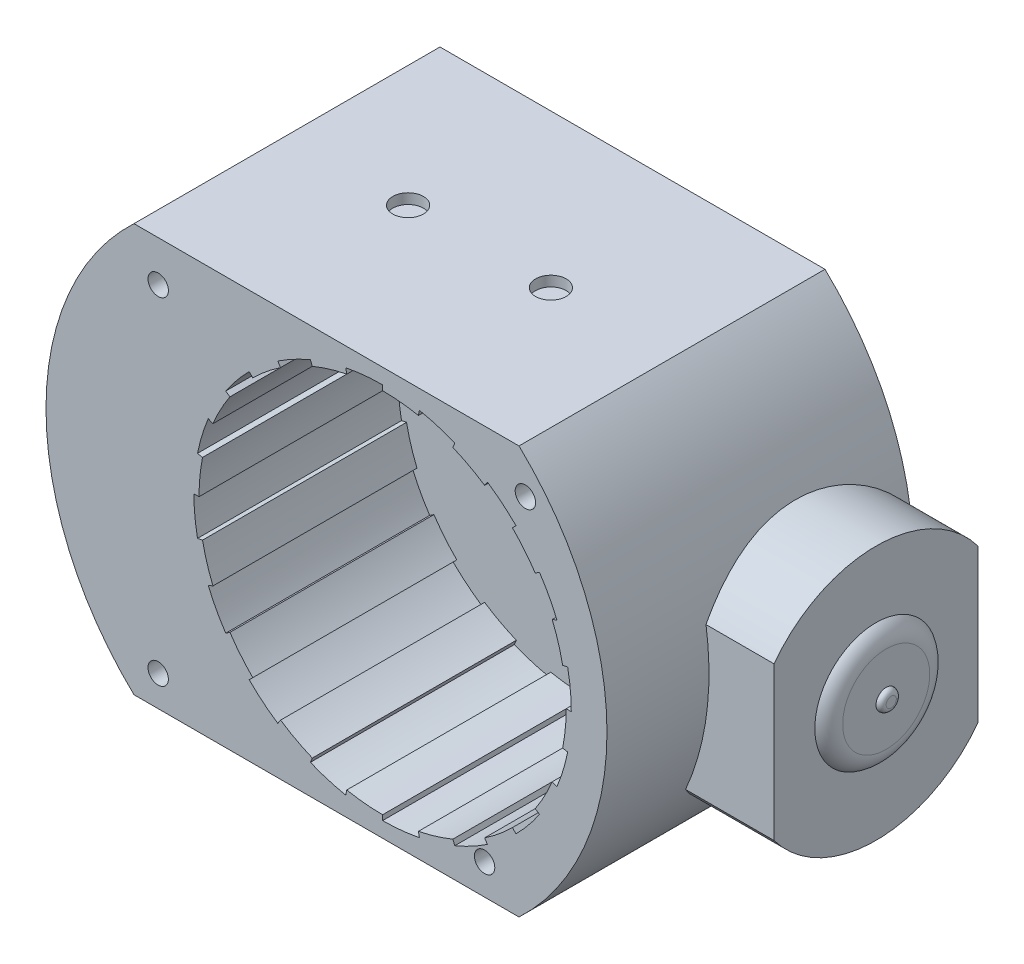
SolidWorks part; units mm, degrees
ref_plane "Alzado" through (0, 0, 0) normal (0, 0, 1) x (1, 0, 0)
ref_plane "Planta" through (0, 0, 0) normal (0, 1, 0) x (1, 0, 0)
ref_plane "Vista lateral" through (0, 0, 0) normal (1, 0, 0) x (0, 0, -1)
sketch "Croquis1" plane through (0, 0, 0) normal (0, 0, 1) x (1, 0, 0)
  line L0 (-27.5, -20) -> (27.5, -20)
  line L1 (-27.5, -20) -> (-27.5, 20)
  line L2 (27.5, -20) -> (27.5, 20)
  line L3 (-27.5, 20) -> (27.5, 20)
  line L4 (-27.5, -20) -> (27.5, 20) construction
  line L5 (27.5, -20) -> (-27.5, 20) construction
  circle A0 centre (0, 0) radius 27.5
  point P1 (0, 0)
  dimension "D1" = 55
  dimension "D2" = 40
extrude "Saliente-Extruir1" add sketch "Croquis1" along normal mid plane 30 contours L3 A0 L0 region at (0, 0, 0)
sketch "Croquis2" plane through (0, 0, 15) normal (0, 0, 1) x (1, 0, 0)
  line L0 (27.5, 0) -> (5.5, 0) construction
  line L1 (5.5, 0) -> (5.5, 18.5)
  line L2 (5.5, 0) -> (9.1092, 18.1445)
  line L3 (5.5, 0) -> (12.5796, 17.0918)
  line L4 (5.5, 0) -> (15.778, 15.3822)
  line L5 (5.5, 0) -> (18.5815, 13.0815)
  line L6 (5.5, 0) -> (20.8822, 10.278)
  line L7 (5.5, 0) -> (22.5918, 7.0796)
  line L8 (5.5, 0) -> (23.6445, 3.6092)
  line L9 (5.5, 0) -> (24, 0)
  line L10 (5.5, 0) -> (23.6445, -3.6092)
  line L11 (5.5, 0) -> (22.5918, -7.0796)
  line L12 (5.5, 0) -> (20.8822, -10.278)
  line L13 (5.5, 0) -> (18.5815, -13.0815)
  line L14 (5.5, 0) -> (15.778, -15.3822)
  line L15 (5.5, 0) -> (12.5796, -17.0918)
  line L16 (5.5, 0) -> (9.1092, -18.1445)
  line L17 (5.5, 0) -> (5.5, -18.5)
  line L18 (5.5, 0) -> (1.8908, -18.1445)
  line L19 (5.5, 0) -> (-1.5796, -17.0918)
  line L20 (5.5, 0) -> (-4.778, -15.3822)
  line L21 (5.5, 0) -> (-7.5815, -13.0815)
  line L22 (5.5, 0) -> (-9.8822, -10.278)
  line L23 (5.5, 0) -> (-11.5918, -7.0796)
  line L24 (5.5, 0) -> (-12.6445, -3.6092)
  line L25 (5.5, 0) -> (-13, 0)
  line L26 (5.5, 0) -> (-12.6445, 3.6092)
  line L27 (5.5, 0) -> (-11.5918, 7.0796)
  line L28 (5.5, 0) -> (-9.8822, 10.278)
  line L29 (5.5, 0) -> (-7.5815, 13.0815)
  line L30 (5.5, 0) -> (-4.778, 15.3822)
  line L31 (5.5, 0) -> (-1.5796, 17.0918)
  line L32 (5.5, 0) -> (1.8908, 18.1445)
  arc A1 (18.8746, -20) -> (18.8746, 20) centre (0, 0) ccw construction
  circle A2 centre (5.5, 0) radius 18.5
  circle A3 centre (5.5, 0) radius 18
  point P45 (5.5, 0)
  dimension "D1" = 22
  dimension "D2" = 37
  dimension "D3" = 0.5
  dimension "D4" = 32
extrude "Cortar-Extruir1" cut sketch "Croquis2" against normal blind 20 contours L2 A3 L1 | L30 A3 L29 | L31 A3 L30 | L32 A3 L31 | L1 A3 L32 | L3 A3 L2 | L4 A3 L3 | L5 A3 L4 | L6 A3 L5 | L7 A3 L6 | L8 A3 L7 | L9 A3 L8 | L10 A3 L9 | L29 A3 L28 | L28 A3 L27 | L27 A3 L26 | L26 A3 L25 | L25 A3 L24 | L24 A3 L23 | L23 A3 L22 | L22 A3 L21 | L21 A3 L20 | L20 A3 L19 | L19 A3 L18 | L18 A3 L17 | L17 A3 L16 | L16 A3 L15 | L15 A3 L14 | L14 A3 L13 | L13 A3 L12 | L12 A3 L11 | L11 A3 L10 | A3 L1 A2 L32 | A3 L31 A2 L30 | A3 L29 A2 L28 | A3 L27 A2 L26 | A3 L25 A2 L24 | A3 L23 A2 L22 | A3 L21 A2 L20 | A3 L19 A2 L18 | A3 L17 A2 L16 | A3 L15 A2 L14 | A3 L13 A2 L12 | A3 L11 A2 L10 | A3 L9 A2 L8 | A3 L7 A2 L6 | A3 L5 A2 L4 | A3 L3 A2 L2 region at (4.3257, 11.923, 15) region at (6.6743, 11.923, 15) region at (8.9778, 11.4648, 15) region at (11.1477, 10.5661, 15) region at (13.1005, 9.2612, 15) region at (14.7612, 7.6005, 15) region at (16.0661, 5.6477, 15) region at (16.9648, 3.4778, 15) region at (17.423, 1.1743, 15) region at (17.423, -1.1743, 15) region at (16.9648, -3.4778, 15) region at (16.0661, -5.6477, 15) region at (14.7612, -7.6005, 15) region at (13.1005, -9.2612, 15) region at (11.1477, -10.5661, 15) region at (8.9778, -11.4648, 15) region at (6.6743, -11.923, 15) region at (4.3257, -11.923, 15) region at (2.0222, -11.4648, 15) region at (-0.1477, -10.5661, 15) region at (-2.1005, -9.2612, 15) region at (-3.7612, -7.6005, 15) region at (-5.0661, -5.6477, 15) region at (-5.9648, -3.4778, 15) region at (-6.423, -1.1743, 15) region at (-6.423, 1.1743, 15) region at (-5.9648, 3.4778, 15) region at (-5.0661, 5.6477, 15) region at (-3.7612, 7.6005, 15) region at (-2.1005, 9.2612, 15) region at (-0.1477, 10.5661, 15) region at (2.0222, 11.4648, 15) region at (3.7139, 18.1341, 15) region at (10.7895, 17.4372, 15) region at (17.0598, 14.0857, 15) region at (21.5702, 8.5897, 15) region at (23.6341, 1.7861, 15) region at (22.9372, -5.2895, 15) region at (19.5857, -11.5598, 15) region at (14.0897, -16.0702, 15) region at (7.2861, -18.1341, 15) region at (0.2105, -17.4372, 15) region at (-6.0598, -14.0857, 15) region at (-10.5702, -8.5897, 15) region at (-12.6341, -1.7861, 15) region at (-11.9372, 5.2895, 15) region at (-8.5857, 11.5598, 15) region at (-3.0897, 16.0702, 15)
ref_plane "Plano1" through (18.8746, 0, 0) normal (1, 0, 0) x (0, 0, -1)
sketch "Croquis3" plane through (18.8746, 0, 0) normal (1, 0, 0) x (0, 0, -1)
  line L0 (15, -20) -> (15, 20) construction
  line L1 (-15, -20) -> (15, -20) construction
  line L2 (-15, 20) -> (15, 20) construction
  line L3 (-15, 20) -> (-15, -20) construction
  line L4 (15, -20) -> (15, 20)
  line L5 (-15, -20) -> (15, -20)
  line L6 (-15, 20) -> (15, 20)
  line L7 (-15, 20) -> (-15, -20)
  line L8 (-15, -16) -> (15, -16)
  line L9 (5, -3.5) -> (15, -3.5) construction
  line L10 (-5, -20) -> (-5, 20)
  circle A0 centre (5, -3.5) radius 12.5
  dimension "D2" = 25
  dimension "D3" = 10
  dimension "D1" = 4
  dimension "D4" = 20
extrude "Saliente-Extruir2" add sketch "Croquis3" along normal blind 15 contours L4 A0 L10 region at (18.8746, -3.5, -5)
sketch "Croquis4" plane through (0, 0, -5) normal (0, 0, 1) x (1, 0, 0)
  circle A0 centre (5.5, 0) radius 1
  dimension "D1" = 2
extrude "Cortar-Extruir2" cut sketch "Croquis4" against normal through all
sketch "Croquis5" plane through (0, 0, -15) normal (0, 0, -1) x (-1, 0, 0)
  circle A0 centre (-5.5, 0) radius 2.5
  circle A1 centre (-5.5, 0) radius 1 construction
  circle A2 centre (-5.5, 0) radius 1
extrude "Saliente-Extruir3" add sketch "Croquis5" along normal blind 5
sketch "Croquis6" plane through (0, 0, -15) normal (0, 0, -1) x (-1, 0, 0)
  line L0 (18.8746, 16) -> (-19.5, 16) construction
  line L1 (-18.8746, -17) -> (18.8746, -17) construction
  line L2 (-5.5, 0) -> (-5.5, 22.7324) construction
  line L3 (-19.5, 0) -> (-19.5, 22.7324) construction
  line L4 (18.8746, 16) -> (-18.8746, 16) construction
  line L5 (-27.2075, 4) -> (-33.8746, 4)
  line L6 (-33.8746, 4) -> (-33.8746, -11)
  line L7 (-33.8746, -11) -> (-25.2042, -11)
  line L8 (-18.8746, -20) -> (18.8746, -20)
  line L9 (18.8746, 20) -> (-18.8746, 20)
  line L10 (-27.2075, 4) -> (-33.8746, 4)
  line L11 (-33.8746, 4) -> (-33.8746, -11)
  line L12 (-33.8746, -11) -> (-25.2042, -11)
  line L13 (-18.8746, -20) -> (18.8746, -20)
  line L14 (18.8746, 20) -> (-18.8746, 20)
  line L15 (-15.5, 0) -> (-15.5, 22.7324) construction
  line L16 (-15.5, -18.657) -> (-15.5, 22.7324) construction
  line L17 (16.5, -19.1964) -> (16.5, 22.7324) construction
  line L18 (16.5, 0) -> (16.5, 22.7324) construction
  circle A0 centre (-19.5, 16) radius 1
  circle A1 centre (-15.5, -17) radius 1
  circle A2 centre (16.5, 16) radius 1
  arc A3 (-18.8746, 20) -> (-27.2075, 4) centre (0, 0) ccw
  arc A4 (-25.2042, -11) -> (-18.8746, -20) centre (0, 0) ccw
  arc A5 (18.8746, -20) -> (18.8746, 20) centre (0, 0) ccw
  arc A6 (-18.8746, 20) -> (-27.2075, 4) centre (0, 0) ccw
  arc A7 (-25.2042, -11) -> (-18.8746, -20) centre (0, 0) ccw
  arc A8 (18.8746, -20) -> (18.8746, 20) centre (0, 0) ccw
  circle A9 centre (16.5, -17) radius 1
  dimension "D5" = 22
  dimension "D7" = 2
  dimension "D1" = 0
  dimension "D2" = 4
  dimension "D3" = 3
  dimension "D4" = 14
  dimension "D6" = 10
extrude "Cortar-Extruir3" cut sketch "Croquis6" along direction (0, 0, 1) on the side against the normal through all contours A0 | A2 | A9 | A1 region at (19.5, 16, -15) region at (-16.5, 16, -15)
sketch "Croquis7" plane through (0, 0, -15) normal (0, 0, -1) x (-1, 0, 0)
  line L0 (-33.8746, -3.5) -> (-15.8034, -3.5) construction
  line L1 (-33.8746, -11) -> (-33.8746, 4) construction
  line L2 (-33.8746, -7.5) -> (-15.8034, -7.5) construction
  line L3 (-15.8034, 0.5) -> (-28.6263, 0.5) construction
  line L4 (-15.8034, -7.5) -> (-28.6263, -7.5) construction
  line L5 (-15.8034, -8.7275) -> (-28.6263, -8.7275)
  line L6 (-15.8034, -6.2725) -> (-28.6263, -6.2725)
  line L7 (-15.8034, 1.7275) -> (-28.6263, 1.7275)
  line L8 (-15.8034, -0.7275) -> (-28.6263, -0.7275)
  arc A0 (-15.8034, -8.7275) -> (-15.8034, -6.2725) centre (-15.8034, -7.5) ccw
  arc A1 (-28.6263, -6.2725) -> (-28.6263, -8.7275) centre (-28.6263, -7.5) ccw
  arc A2 (-15.8034, 1.7275) -> (-15.8034, -0.7275) centre (-15.8034, 0.5) cw
  arc A3 (-28.6263, -0.7275) -> (-28.6263, 1.7275) centre (-28.6263, 0.5) cw
  point P8 (-22.2149, -7.5)
  point P14 (-22.2149, 0.5)
  dimension "D1" = 4
extrude "Cortar-Extruir4" cut sketch "Croquis7" against normal blind 5
sketch "Croquis8" plane through (33.8746, 0, 0) normal (1, 0, 0) x (0, 0, -1)
  circle A0 centre (5, -3.5) radius 6
extrude "Saliente-Extruir4" add sketch "Croquis8" along normal blind 1
fillet "Redondeo1" radius 2 1 edges at (34.8746, -3.5, -11)
sketch "Croquis9" plane through (34.8746, 0, 0) normal (1, 0, 0) x (0, 0, -1)
  circle A0 centre (5, -3.5) radius 1
extrude "Saliente-Extruir5" add sketch "Croquis9" along normal blind 0.4927
fillet "Redondeo2" radius 0.5 1 edges at (35.3673, -3.5, -6)
sketch "Croquis15" plane through (0, 20, 0) normal (0, 1, 0) x (1, 0, 0)
  line L0 (0, -15) -> (0, 15) construction
  line L1 (18.8746, 0) -> (-18.8746, 0) construction
  line L2 (7, -15) -> (7, 15) construction
  line L3 (-7, -15) -> (-7, 15) construction
  line L4 (18.8746, 15) -> (-18.8746, 15)
  line L5 (18.8746, 15) -> (-18.8746, 15)
  line L6 (-18.8746, -15) -> (18.8746, -15)
  line L7 (18.8746, -15) -> (18.8746, 15)
  line L8 (-18.8746, 15) -> (-18.8746, -15)
  line L9 (-18.8746, 15) -> (-18.8746, -15)
  line L10 (-18.8746, -15) -> (18.8746, -15) construction
  line L11 (18.8746, -15) -> (18.8746, 15) construction
  circle A0 centre (-7, 0) radius 1.5
  circle A1 centre (7, 0) radius 1.5
  dimension "D4" = 3
  dimension "D1" = 0
  dimension "D2" = 7
  dimension "D3" = 7
extrude "Cortar-Extruir16" cut sketch "Croquis15" against normal blind 1 contours A1 | A0 region at (-7, 20, 0) region at (7, 20, 0)
ref_plane "Plano2" through (-27.5, 0, 0) normal (1, 0, 0) x (0, 0, -1)
mirror "Simetría1" about plane through (0, 0, 0) normal (0, 1, 0) of "Cortar-Extruir16"
sketch "Croquis16" plane through (0, 0, -15) normal (0, 0, -1) x (-1, 0, 0)
  line L0 (-5.5, 0) -> (-5.5, 22.0955) construction
  line L1 (-5.5, 0) -> (-38.0603, 0) construction
